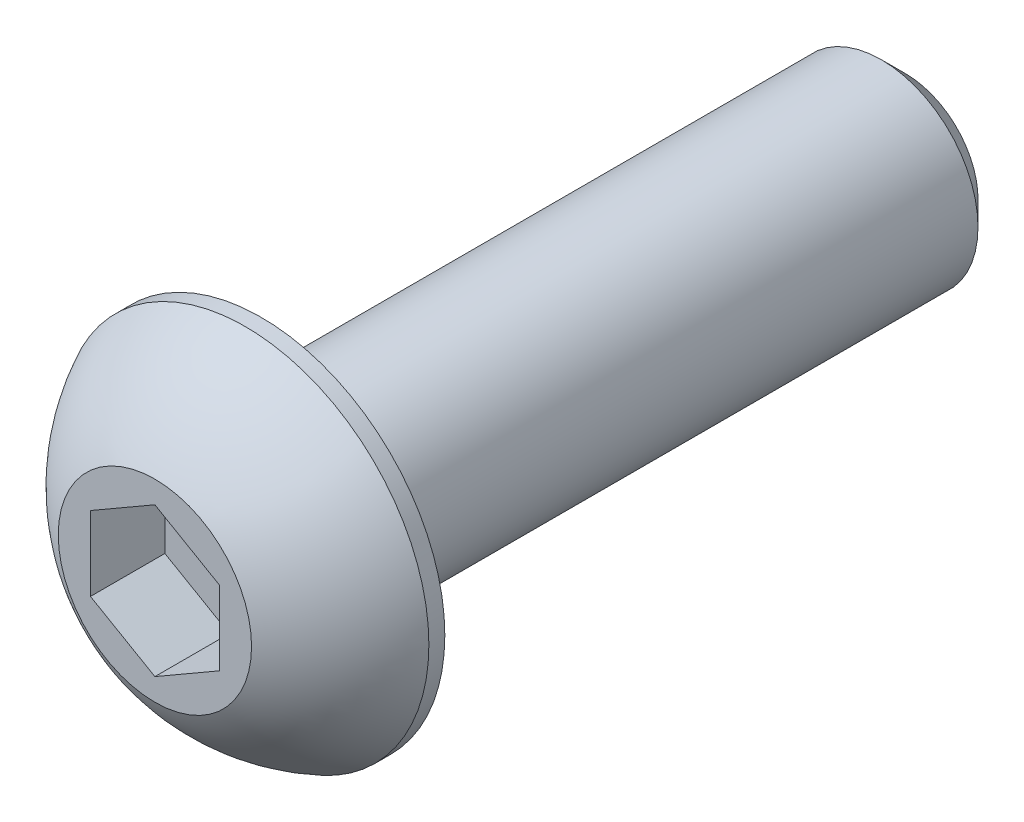
SolidWorks part; units mm, degrees
ref_plane "Front" through (0, 0, 0) normal (0, 0, 1) x (1, 0, 0)
ref_plane "Top" through (0, 0, 0) normal (0, 1, 0) x (1, 0, 0)
ref_plane "Right" through (0, 0, 0) normal (1, 0, 0) x (0, 0, -1)
sketch "Sketch1" plane through (0, 0, 0) normal (1, 0, 0) x (0, 0, -1)
  line L2 (1.65, 1.5) -> (11.65, 1.5)
  line L3 (11.65, 1.5) -> (11.65, 0)
  line L4 (11.65, 0) -> (1.65, 0)
  line L6 (1.4025, 2.85) -> (1.65, 2.85) construction
  line L7 (11.65, 1.5) -> (11.65, -1.5) construction
  line L8 (0, 0) -> (1.65, 0) construction
  line L9 (1.65, 2.85) -> (1.65, -2.85) construction
  line L11 (1.65, 1.5) -> (1.65, 0)
  line L13 (0, 1) -> (0, -1) construction
  line L14 (0, 1) -> (0, 1.5) construction
  arc A3 (0, 1.5) -> (1.4025, 2.85) centre (2.7948, 0) cw construction
  dimension "D1" = 0.2475
revolve "Revolve1" add sketch "Sketch1" angle 360 mid plane about L4
sketch "Sketch3" plane through (0, 0, -11.65) normal (0, 0, -1) x (-1, 0, 0)
  circle A0 centre (0, 0) radius 1.5
curve "Helix/Spiral1" [suppressed] pitch 0.5 height 10.5 turns 21
chamfer "Chamfer1" distance 0.375 angle 45 1 edges at (0, 1.5, -11.65)
sketch "Sketch7" plane through (0, 0, 0) normal (1, 0, 0) x (0, 0, -1)
  line L6 (1.4025, 2.85) -> (1.65, 2.85) construction
  line L8 (0, 0) -> (1.65, 0) construction
  line L11 (1.65, 2.85) -> (1.65, -2.85) construction
  line L12 (1.4025, 2.85) -> (1.65, 2.85)
  line L13 (0, 0) -> (1.65, 0)
  line L14 (0, 1) -> (0, -1) construction
  line L15 (1.65, 2.85) -> (1.65, 0)
  line L16 (0, 1.5) -> (0, 0)
  arc A2 (1.4025, 2.85) -> (0, 1.5) centre (2.7948, 0) ccw construction
  arc A3 (1.4025, 2.85) -> (0, 1.5) centre (2.7948, 0) ccw
revolve "Revolve2" add sketch "Sketch7" angle 360 mid plane about L13
sketch "Sketch5" plane through (0, 0, 0) normal (0, 0, 1) x (1, 0, 0)
  line L1 (1, -0.5774) -> (1, 0.5774)
  line L2 (1, 0.5774) -> (0, 1.1547)
  line L3 (0, 1.1547) -> (-1, 0.5774)
  line L4 (-1, 0.5774) -> (-1, -0.5774)
  line L5 (-1, -0.5774) -> (0, -1.1547)
  line L6 (0, -1.1547) -> (1, -0.5774)
  circle A0 centre (0, 0) radius 1 construction
extrude "Cut-Extrude2" cut sketch "Sketch5" against normal blind 1.155
sketch "Sketch6" plane through (0, 0, 0) normal (0, 0, 1) x (1, 0, 0)
  circle A0 centre (0, 0) radius 1.1547
extrude "Cut-Extrude3" [suppressed] cut sketch "Sketch6" against normal blind 1.155 draft 45
sketch "Sketch2" plane through (0, 0, 0) normal (1, 0, 0) x (0, 0, -1)
  line L0 (11.275, 1.5) -> (11.7125, 1.5)
  line L1 (11.7125, 1.5) -> (11.525, 1.1752)
  line L2 (11.525, 1.1752) -> (11.4625, 1.1752)
  line L3 (11.4625, 1.1752) -> (11.275, 1.5)
  line L4 (11.3688, 1.3376) -> (11.6188, 1.3376) construction
  dimension "D1" = 60
  dimension "D2" = 0.0625
  dimension "D3" = 0.25
sweep "Cut-Sweep1" [suppressed] cut profiles "Sketch2" path "Helix/Spiral1"
sketch "Sketch10" plane through (0, 0, 0) normal (1, 0, 0) x (0, 0, -1)
  line L0 (11.65, 1.5) -> (11.65, -1.5) construction
  point P0 (10.9, -1.5)
  dimension "D1" = 0.75
ref_axis "Center Axis 1" through (0, 0, -8.1113) along (0, 0, 1)
ref_plane "Contact Plane 1" through (0, 0, -1.65) normal (0, 0, -1) x (-1, 0, 0)
ref_plane "Contact Plane 2" through (0, 0, 0) normal (0, 0, 1) x (1, 0, 0)
equation "\"D3@Helix/Spiral1\" = \"Lg@Sketch1\" + \"D4@Helix/Spiral1\""
equation "\"D2@Sketch2\" = \"D4@Helix/Spiral1\" * .125"
equation "\"D3@Sketch2\" = \"D4@Helix/Spiral1\" * .5"
equation "\"D1@Chamfer1\" = \"D4@Helix/Spiral1\" * .75"
equation "\"D1@Cut-Extrude2\" = \"Head Ht@Sketch1\" * .7"
equation "\"D1@Sketch1\" = \"Head Ht@Sketch1\" * .15"
equation "\"D1@Sketch10\" = \"D4@Helix/Spiral1\" * 1.5"
equation "\"D1@Cut-Extrude3\" = \"D1@Cut-Extrude2\""
